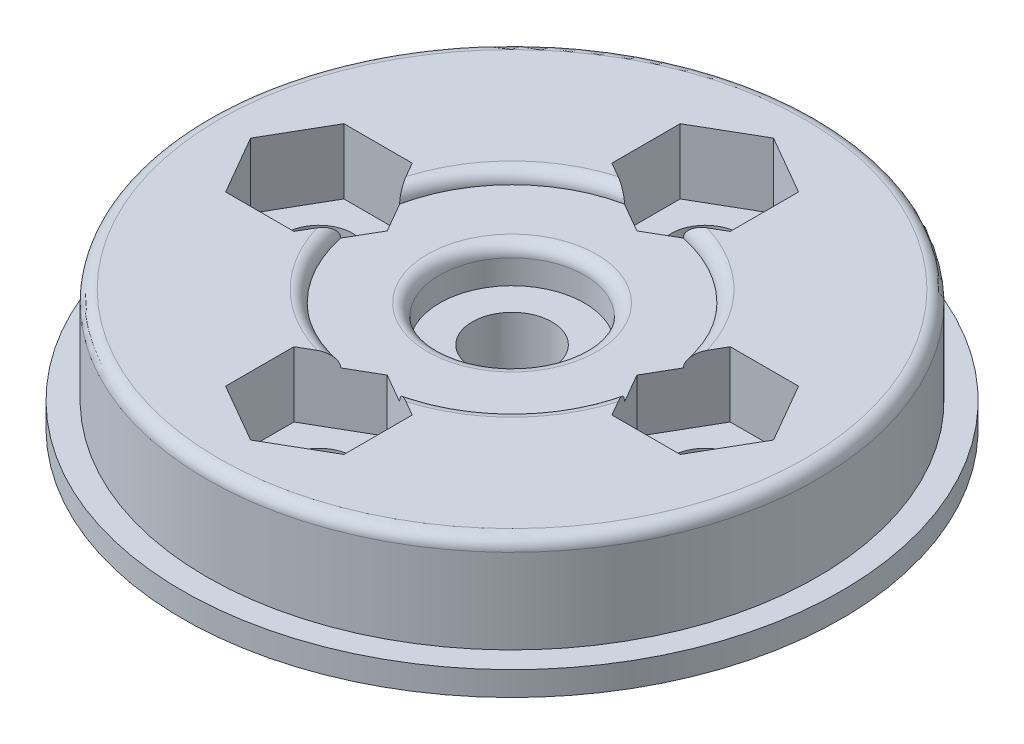
SolidWorks part; units mm, degrees
ref_plane "Front Plane" through (0, 0, 0) normal (0, 0, 1) x (1, 0, 0)
ref_plane "Top Plane" through (0, 0, 0) normal (0, 1, 0) x (1, 0, 0)
ref_plane "Right Plane" through (0, 0, 0) normal (1, 0, 0) x (0, 0, -1)
sketch "Sketch1" plane through (0, 0, 0) normal (0, 1, 0) x (1, 0, 0)
  circle A0 centre (0, 0) radius 12.65
  dimension "D1" = 25.3
extrude "Boss-Extrude1" add sketch "Sketch1" along normal blind 4
sketch "Sketch2" plane through (0, 4, 0) normal (0, 1, 0) x (1, 0, 0)
  line L0 (-2.75, 12.1) -> (-2.75, 12.3475)
  line L1 (2.75, 12.1) -> (2.75, 12.3475)
  line L2 (12.1, -2.75) -> (12.3475, -2.75)
  line L3 (12.1, 2.75) -> (12.3475, 2.75)
  line L4 (-2.75, -12.1) -> (-2.75, -12.3475)
  line L5 (2.75, -12.1) -> (2.75, -12.3475)
  line L6 (-12.1, 2.75) -> (-12.3475, 2.75)
  line L7 (-12.1, -2.75) -> (-12.3475, -2.75)
  circle A0 centre (0, 0) radius 12.1 construction
  arc A1 (-2.75, 12.1) -> (2.75, 12.1) centre (0, 12.1) ccw
  circle A2 centre (0, 0) radius 12.65 construction
  arc A3 (-2.75, 12.3475) -> (2.75, 12.3475) centre (0, 0) cw
  arc A4 (12.1, 2.75) -> (12.1, -2.75) centre (12.1, 0) ccw
  arc A5 (12.3475, 2.75) -> (12.3475, -2.75) centre (0, 0) cw
  arc A6 (2.75, -12.1) -> (-2.75, -12.1) centre (0, -12.1) ccw
  arc A7 (2.75, -12.3475) -> (-2.75, -12.3475) centre (0, 0) cw
  arc A8 (-12.1, -2.75) -> (-12.1, 2.75) centre (-12.1, 0) ccw
  arc A9 (-12.3475, -2.75) -> (-12.3475, 2.75) centre (0, 0) cw
  point P29 (0, 0)
  dimension "D1" = 24.2
  dimension "D2" = 5.5
  dimension "D3" = 4
extrude "Cut-Extrude1" [suppressed] cut sketch "Sketch2" against normal blind 0.55
sketch "Sketch3" [suppressed] plane through (0, 1.45, 0) normal (0, 1, 0) x (1, 0, 0)
  circle A0 centre (0, 12.1) radius 1.4
  circle A1 centre (-12.1, 0) radius 1.4
  circle A2 centre (0, -12.1) radius 1.4
  circle A3 centre (12.1, 0) radius 1.4
  dimension "D1" = 2.8
extrude "Cut-Extrude2" [suppressed] cut sketch "Sketch3" against normal blind 2.55
sketch "Sketch4" plane through (0, 4, 0) normal (0, 1, 0) x (1, 0, 0)
  circle A0 centre (0, 0) radius 6
  dimension "D1" = 12
extrude "Cut-Extrude3" cut sketch "Sketch4" against normal blind 0.5
sketch "Sketch5" plane through (0, 3.5, 0) normal (0, 1, 0) x (1, 0, 0)
  circle A0 centre (0, 0) radius 3
  dimension "D1" = 6
extrude "Cut-Extrude4" cut sketch "Sketch5" against normal blind 1.5
fillet "Fillet1" radius 0.5 1 edges at (0, 4, 6)
fillet "Fillet2" radius 0.5 1 edges at (0, 3.5, 3)
fillet "Fillet3" radius 0.5 1 edges at (0, 4, 12.65)
sketch "Sketch7" plane through (0, 0, 0) normal (0, -1, 0) x (1, 0, 0)
  circle A0 centre (0, 0) radius 13.65
  circle A1 centre (0, 0) radius 12.65 construction
  dimension "D1" = 1
extrude "Boss-Extrude2" add sketch "Sketch7" along normal blind 1
sketch "Sketch8" plane through (0, 4, 0) normal (0, 1, 0) x (1, 0, 0)
  circle A0 centre (0, 0) radius 8 construction
  circle A1 centre (0, 8) radius 1.4
  circle A2 centre (8, 0) radius 1.4
  circle A3 centre (0, -8) radius 1.4
  circle A4 centre (-8, 0) radius 1.4
  point P14 (0, 0)
  dimension "D1" = 16
  dimension "D2" = 2.8
  dimension "D3" = 4
hole_wizard "CSK for M3 Flat Head Machine Screw1" [suppressed] positions "Sketch12" profile "Sketch11" countersink size "M3" standard "ANSI Metric"
sketch "Sketch12" plane through (0, 3, 0) normal (0, 1, 0) x (1, 0, 0)
  point P0 (0, 8)
  point P3 (-8, 0)
  point P6 (0, -8)
  point P9 (8, 0)
sketch "Sketch11" plane through (0, 3, -8) normal (1, 0, 0) x (0, 0, 1)
  line L0 (0, 0) -> (0, 6.0215)
  line L1 (0, 6.0215) -> (1.7, 5)
  line L2 (1.7, 5) -> (1.7, 1.45)
  line L3 (1.7, 1.45) -> (3.15, 0)
  line L5 (3.15, 0) -> (0, 0)
  line L6 (-1.7, 1.45) -> (-3.15, 0) construction
  line L10 (0, 6.0215) -> (-1.7, 5) construction
  line L11 (0, -6.35) -> (0, 107.95) construction
  dimension "Hole Dia." = 3.4
  dimension "Hole Depth" = 5
  dimension "Near C'Sink Dia." = 6.3
  dimension "Near C'Sink Angle" = 90
  dimension "Drill Angle" = 118
sketch "Sketch13" [suppressed] plane through (0, 3, 0) normal (0, 1, 0) x (1, 0, 0)
  circle A0 centre (0, 8) radius 3.15
  circle A1 centre (8, 0) radius 3.15
  circle A2 centre (0, -8) radius 3.15
  circle A3 centre (-8, 0) radius 3.15
  arc A4 (-2.0748, 5.6298) -> (2.0748, 5.6298) centre (0, 8) ccw construction
  point P12 (0, 0)
  dimension "D1" = 4
extrude "Cut-Extrude5" [suppressed] cut sketch "Sketch13" along normal through all
extrude "Cut-Extrude6" cut sketch "Sketch8" against normal through all
sketch "Sketch15" plane through (0, 4, 0) normal (0, 1, 0) x (1, 0, 0)
  line L0 (5.171, 0) -> (6.5855, -2.45)
  line L1 (0, 5.171) -> (2.45, 6.5855)
  line L2 (2.45, 6.5855) -> (2.45, 9.4145)
  line L3 (2.45, 9.4145) -> (0, 10.829)
  line L4 (0, 10.829) -> (-2.45, 9.4145)
  line L5 (-2.45, 9.4145) -> (-2.45, 6.5855)
  line L6 (-2.45, 6.5855) -> (0, 5.171)
  line L7 (6.5855, -2.45) -> (9.4145, -2.45)
  line L8 (9.4145, -2.45) -> (10.829, 0)
  line L9 (10.829, 0) -> (9.4145, 2.45)
  line L10 (9.4145, 2.45) -> (6.5855, 2.45)
  line L11 (6.5855, 2.45) -> (5.171, 0)
  line L12 (0, -5.171) -> (-2.45, -6.5855)
  line L13 (-2.45, -6.5855) -> (-2.45, -9.4145)
  line L14 (-2.45, -9.4145) -> (0, -10.829)
  line L15 (0, -10.829) -> (2.45, -9.4145)
  line L16 (2.45, -9.4145) -> (2.45, -6.5855)
  line L17 (2.45, -6.5855) -> (0, -5.171)
  line L18 (-5.171, 0) -> (-6.5855, 2.45)
  line L19 (-6.5855, 2.45) -> (-9.4145, 2.45)
  line L20 (-9.4145, 2.45) -> (-10.829, 0)
  line L21 (-10.829, 0) -> (-9.4145, -2.45)
  line L22 (-9.4145, -2.45) -> (-6.5855, -2.45)
  line L23 (-6.5855, -2.45) -> (-5.171, 0)
  circle A0 centre (0, 8) radius 2.45 construction
  point P30 (0, 0)
  dimension "D1" = 4.9
  dimension "D2" = 4
extrude "Cut-Extrude7" cut sketch "Sketch15" against normal blind 2.7
sketch "Sketch16" plane through (0, 2, 0) normal (0, 1, 0) x (1, 0, 0)
  circle A0 centre (0, 0) radius 1.65
  dimension "D1" = 3.3
extrude "Cut-Extrude8" cut sketch "Sketch16" against normal blind 10
